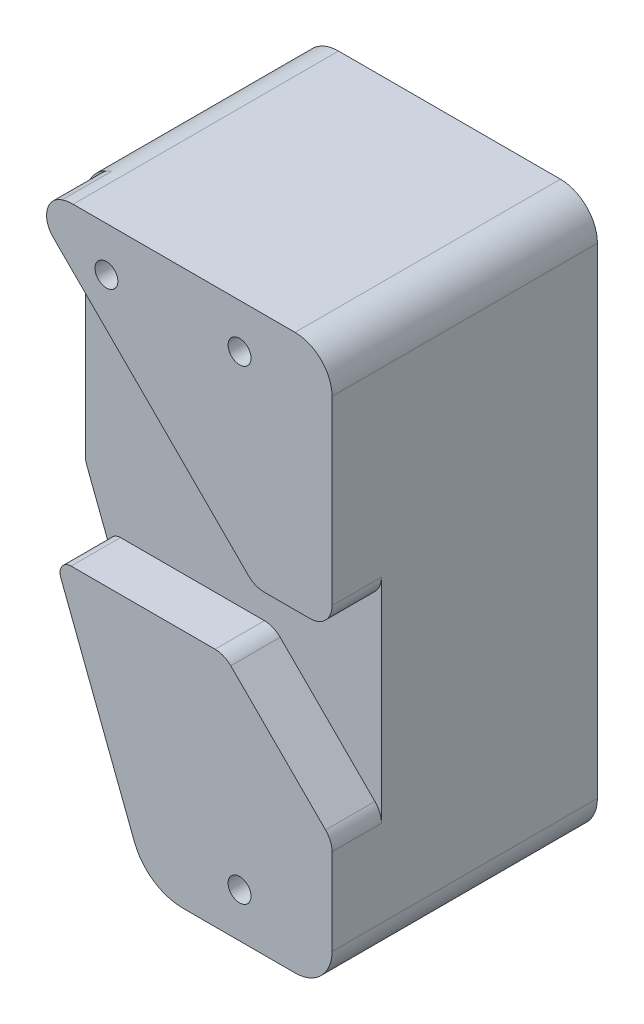
SolidWorks part; units mm, degrees
ref_plane "Front Plane" through (0, 0, 0) normal (0, 0, 1) x (1, 0, 0)
ref_plane "Top Plane" through (0, 0, 0) normal (0, 1, 0) x (1, 0, 0)
ref_plane "Right Plane" through (0, 0, 0) normal (1, 0, 0) x (0, 0, -1)
sketch "Sketch1" plane through (0, 0, 0) normal (0, 0, 1) x (1, 0, 0)
  line L0 (12.5, 69) -> (12.5, 6) construction
  line L1 (0, 0) -> (25, 0)
  line L2 (0, 0) -> (0, 75)
  line L3 (0, 75) -> (25, 75)
  line L4 (25, 0) -> (25, 75)
  line L6 (0, 75) -> (-15, 75)
  line L7 (0, 75) -> (0, 37.5)
  line L8 (0, 37.5) -> (-15, 37.5)
  line L9 (-15, 75) -> (-15, 37.5)
  circle A0 centre (12.5, 69) radius 1.5
  circle A1 centre (12.5, 6) radius 1.5
  circle A2 centre (12.5, 37.5) radius 1.5
  dimension "D3" = 3
  dimension "D4" = 3
  dimension "D7" = 3
  dimension "D1" = 75
  dimension "D2" = 25
  dimension "D5" = 6
  dimension "D6" = 6
  dimension "D8" = 0
  dimension "D9" = 12.5
  dimension "D10" = 15
extrude "Boss-Extrude1" add sketch "Sketch1" along normal blind 2.85 contours L6 L9 L8 L2 | L1 L4 L3 L2 A0 A2 A1 region at (0.7906, 18.75, 0) region at (-7.5, 56.25, 0)
fillet "Fillet1" radius 5 5 edges at (25, 0, 1.425) (0, 0, 1.425) (25, 75, 1.425) (-15, 75, 1.425) (0, 37.5, 1.425)
fillet "Fillet2" radius 2 1 edges at (-15, 37.5, 1.425)
sketch "Sketch5" plane through (0, 0, 2.85) normal (0, 0, 1) x (1, 0, 0)
  line L0 (0, 25) -> (25, 50)
  line L3 (-17.5, 42.5) -> (42.5, 42.5)
  line L4 (42.5, 32.5) -> (42.5, 42.5)
  line L5 (-0.8417, 35.2764) -> (42.5, 42.5) construction
  line L6 (-17.5, 42.5) -> (42.5, 32.5) construction
  line L7 (0, 17.9289) -> (25, 42.9289)
  line L8 (0, 32.0711) -> (21.4645, 53.5355)
  line L9 (-20.8226, 11.2484) -> (21.4645, 53.5355) construction
  line L10 (-17.2871, 7.7129) -> (25, 50) construction
  line L11 (-13.7516, 4.1774) -> (28.5355, 46.4645) construction
  line L12 (21.4645, 53.5355) -> (25, 57.0711)
  line L13 (-15, 70) -> (-15, 39.5)
  line L14 (-13, 37.5) -> (-5, 37.5)
  line L15 (0, 32.5) -> (0, 5)
  line L16 (5, 0) -> (20, 0)
  line L17 (25, 5) -> (25, 70)
  line L18 (20, 75) -> (-10, 75)
  line L19 (-15, 70) -> (-15, 39.5)
  line L20 (-13, 37.5) -> (-5, 37.5)
  line L21 (0, 32.5) -> (0, 5)
  line L22 (5, 0) -> (20, 0)
  line L23 (25, 5) -> (25, 70)
  line L24 (20, 75) -> (-10, 75)
  line L25 (42.5, 32.5) -> (14.5711, 32.5)
  arc A6 (-15, 39.5) -> (-13, 37.5) centre (-13, 39.5) ccw
  arc A7 (0, 32.5) -> (-5, 37.5) centre (-5, 32.5) ccw
  arc A8 (0, 5) -> (5, 0) centre (5, 5) ccw
  arc A9 (20, 0) -> (25, 5) centre (20, 5) ccw
  arc A10 (25, 70) -> (20, 75) centre (20, 70) ccw
  arc A11 (-10, 75) -> (-15, 70) centre (-10, 70) ccw
  arc A12 (-15, 39.5) -> (-13, 37.5) centre (-13, 39.5) ccw
  arc A13 (0, 32.5) -> (-5, 37.5) centre (-5, 32.5) ccw
  arc A14 (0, 5) -> (5, 0) centre (5, 5) ccw
  arc A15 (20, 0) -> (25, 5) centre (20, 5) ccw
  arc A16 (25, 70) -> (20, 75) centre (20, 70) ccw
  arc A17 (-10, 75) -> (-15, 70) centre (-10, 70) ccw
  point P0 (12.5, 37.5)
  point P9 (12.5, 37.5)
  line M2 (-15, 70) -> (-15, 39.5)
  line M6 (0, 32.5) -> (0, 5)
  arc M7 (0, 5) -> (5, 0) centre (5, 5) ccw
  line M8 (5, 0) -> (20, 0)
  arc M9 (20, 0) -> (25, 5) centre (20, 5) ccw
  line M10 (25, 5) -> (25, 70)
  arc M11 (25, 70) -> (20, 75) centre (20, 70) ccw
  line M12 (20, 75) -> (-10, 75)
  arc M13 (-10, 75) -> (-15, 70) centre (-10, 70) ccw
  circle M15 centre (12.5, 6) radius 1.5
  circle M16 centre (12.5, 69) radius 1.5
  dimension "D3" = 0
  dimension "D4" = 5
  dimension "D5" = 5
extrude "Boss-Extrude2" add sketch "Sketch5" along normal blind 3.5 contours L8 L12 L3 M10 M11 M12 M13 M2 M16 | L25 L7 M10 M6 M7 M8 M9 M15 region at (13.6784, 14.8345, 2.85) region at (3.588, 59.5787, 2.85)
fillet "Fillet3" radius 3.5 2 edges at (14.5711, 32.5, 4.6) (10.4289, 42.5, 4.6)
fillet "Fillet4" radius 2 1 edges at (-15, 42.5, 4.6)
fillet "Fillet5" radius 2 3 edges at (0, 17.9289, 4.6) (25, 32.5, 4.6) (25, 57.0711, 4.6)
sketch "Sketch6" plane through (0, 0, 6.35) normal (0, 0, 1) x (1, 0, 0)
  circle A0 centre (-5.5, 69) radius 1.5
  circle A1 centre (12.5, 69) radius 1.5 construction
  dimension "D1" = 3
  dimension "D2" = 18
extrude "Cut-Extrude1" cut sketch "Sketch6" against normal blind 10
sketch "Sketch8" plane through (0, 0, 0) normal (0, 0, -1) x (-1, 0, 0)
  line L6 (5, 37.5) -> (13, 37.5)
  line L7 (15, 39.5) -> (15, 70)
  line L8 (10, 75) -> (-20, 75)
  line L9 (-25, 70) -> (-25, 5)
  line L10 (-20, 0) -> (-5, 0)
  line L11 (0, 5) -> (0, 32.5)
  line L12 (5, 37.5) -> (13, 37.5)
  line L13 (15, 39.5) -> (15, 70)
  line L14 (10, 75) -> (-20, 75)
  line L15 (-25, 70) -> (-25, 5)
  line L16 (-20, 0) -> (-5, 0)
  line L17 (0, 5) -> (0, 32.5)
  arc A6 (13, 37.5) -> (15, 39.5) centre (13, 39.5) ccw
  arc A7 (15, 70) -> (10, 75) centre (10, 70) ccw
  arc A8 (-20, 75) -> (-25, 70) centre (-20, 70) ccw
  arc A9 (-25, 5) -> (-20, 0) centre (-20, 5) ccw
  arc A10 (-5, 0) -> (0, 5) centre (-5, 5) ccw
  arc A11 (5, 37.5) -> (0, 32.5) centre (5, 32.5) ccw
  arc A12 (13, 37.5) -> (15, 39.5) centre (13, 39.5) ccw
  arc A13 (15, 70) -> (10, 75) centre (10, 70) ccw
  arc A14 (-20, 75) -> (-25, 70) centre (-20, 70) ccw
  arc A15 (-25, 5) -> (-20, 0) centre (-20, 5) ccw
  arc A16 (-5, 0) -> (0, 5) centre (-5, 5) ccw
  arc A17 (5, 37.5) -> (0, 32.5) centre (5, 32.5) ccw
  circle M13 centre (5.5, 69) radius 1.5
  line M14 (5, 37.5) -> (13, 37.5)
  arc M15 (13, 37.5) -> (15, 39.5) centre (13, 39.5) ccw
  line M16 (15, 39.5) -> (15, 70)
  arc M17 (15, 70) -> (10, 75) centre (10, 70) ccw
  line M18 (10, 75) -> (-20, 75)
  arc M19 (-20, 75) -> (-25, 70) centre (-20, 70) ccw
  line M20 (-25, 70) -> (-25, 5)
  arc M21 (-25, 5) -> (-20, 0) centre (-20, 5) ccw
  line M22 (-20, 0) -> (-5, 0)
  arc M23 (-5, 0) -> (0, 5) centre (-5, 5) ccw
  line M24 (0, 5) -> (0, 32.5)
  arc M25 (0, 32.5) -> (5, 37.5) centre (5, 32.5) cw
  circle M26 centre (-12.5, 37.5) radius 1.5
  circle M27 centre (-12.5, 6) radius 1.5
  circle M28 centre (-12.5, 69) radius 1.5
  dimension "D1" = 0
extrude "Boss-Extrude3" add sketch "Sketch8" along normal blind 6.35 contours M25 M14 M15 M16 M17 M18 M19 M20 M21 M22 M23 M24 M27 M28 M26 M13 region at (7.8634, 41.813, 0)
sketch "Sketch9" plane through (0, 0, 6.35) normal (0, 0, 1) x (1, 0, 0)
  line L0 (13.5459, 31.4749) -> (0.5858, 18.5147) construction
  line L1 (0, 17.1005) -> (0, 5) construction
  line L2 (5, 0) -> (20, 0) construction
  line L3 (25, 5) -> (25, 30.5) construction
  line L4 (23, 32.5) -> (16.0208, 32.5) construction
  line L5 (11.4541, 43.5251) -> (24.4142, 56.4853) construction
  line L6 (25, 57.8995) -> (25, 70) construction
  line L7 (20, 75) -> (-10, 75) construction
  line L8 (-15, 70) -> (-15, 44.5) construction
  line L9 (-13, 42.5) -> (8.9792, 42.5) construction
  line L10 (13.5459, 31.4749) -> (0.5858, 18.5147)
  line L11 (0, 17.1005) -> (0, 5)
  line L12 (5, 0) -> (20, 0)
  line L13 (25, 5) -> (25, 30.5)
  line L14 (23, 32.5) -> (16.0208, 32.5)
  line L15 (11.4541, 43.5251) -> (24.4142, 56.4853)
  line L16 (25, 57.8995) -> (25, 70)
  line L17 (20, 75) -> (-10, 75)
  line L18 (-15, 70) -> (-15, 44.5)
  line L19 (-13, 42.5) -> (8.9792, 42.5)
  arc A0 (0.5858, 18.5147) -> (0, 17.1005) centre (2, 17.1005) ccw construction
  arc A1 (0, 5) -> (5, 0) centre (5, 5) ccw construction
  arc A2 (20, 0) -> (25, 5) centre (20, 5) ccw construction
  arc A3 (25, 30.5) -> (23, 32.5) centre (23, 30.5) ccw construction
  arc A4 (16.0208, 32.5) -> (13.5459, 31.4749) centre (16.0208, 29) ccw construction
  arc A5 (24.4142, 56.4853) -> (25, 57.8995) centre (23, 57.8995) ccw construction
  arc A6 (25, 70) -> (20, 75) centre (20, 70) ccw construction
  arc A7 (-10, 75) -> (-15, 70) centre (-10, 70) ccw construction
  arc A8 (-15, 44.5) -> (-13, 42.5) centre (-13, 44.5) ccw construction
  arc A9 (8.9792, 42.5) -> (11.4541, 43.5251) centre (8.9792, 46) ccw construction
  arc A10 (0.5858, 18.5147) -> (0, 17.1005) centre (2, 17.1005) ccw
  arc A11 (0, 5) -> (5, 0) centre (5, 5) ccw
  arc A12 (20, 0) -> (25, 5) centre (20, 5) ccw
  arc A13 (25, 30.5) -> (23, 32.5) centre (23, 30.5) ccw
  arc A14 (16.0208, 32.5) -> (13.5459, 31.4749) centre (16.0208, 29) ccw
  arc A15 (24.4142, 56.4853) -> (25, 57.8995) centre (23, 57.8995) ccw
  arc A16 (25, 70) -> (20, 75) centre (20, 70) ccw
  arc A17 (-10, 75) -> (-15, 70) centre (-10, 70) ccw
  arc A18 (-15, 44.5) -> (-13, 42.5) centre (-13, 44.5) ccw
  arc A19 (8.9792, 42.5) -> (11.4541, 43.5251) centre (8.9792, 46) ccw
  circle M1 centre (-5.5, 69) radius 1.5
  circle M2 centre (12.5, 69) radius 1.5
  line M3 (11.4541, 43.5251) -> (24.4142, 56.4853)
  arc M4 (24.4142, 56.4853) -> (25, 57.8995) centre (23, 57.8995) ccw
  line M5 (25, 57.8995) -> (25, 70)
  arc M6 (25, 70) -> (20, 75) centre (20, 70) ccw
  line M7 (20, 75) -> (-10, 75)
  arc M8 (-10, 75) -> (-15, 70) centre (-10, 70) ccw
  line M9 (-15, 70) -> (-15, 44.5)
  arc M10 (-15, 44.5) -> (-13, 42.5) centre (-13, 44.5) ccw
  line M11 (-13, 42.5) -> (8.9792, 42.5)
  arc M12 (8.9792, 42.5) -> (11.4541, 43.5251) centre (8.9792, 46) ccw
extrude "Boss-Extrude4" add sketch "Sketch9" along normal blind 3.175 contours M12 M3 M4 M5 M6 M7 M8 M9 M10 M11 M2 M1 | L14 A14 L10 A10 L11 A11 L12 A12 L13 A13 region at (13.6542, 14.7163, 6.35) region at (3.6533, 59.5379, 6.35)
sketch "Sketch10" plane through (0, 0, 9.525) normal (0, 0, 1) x (1, 0, 0)
  line L1 (25, 57.8995) -> (-15, 57.8995)
  line L2 (25, 57.8995) -> (25, 42.5)
  line L3 (25, 42.5) -> (-15, 42.5)
  line L4 (-15, 57.8995) -> (-15, 42.5)
  line L5 (25, 32.5) -> (0, 32.5)
  line L6 (25, 32.5) -> (25, 17.1005)
  line L7 (25, 17.1005) -> (0, 17.1005)
  line L8 (0, 32.5) -> (0, 17.1005)
  point P0 (-13, 42.5)
  point P1 (-15, 44.5)
  point P8 (25, 32.5)
extrude "Boss-Extrude5" add sketch "Sketch10" against normal up to surface (6.675 mm away) up to face at (5.4763, 37.3513, 2.85)
sketch "Sketch11" plane through (0, 0, 9.525) normal (0, 0, 1) x (1, 0, 0)
  line L0 (8.9645, 33.9645) -> (0.4289, 42.5)
  line L1 (-15, 42.5) -> (25, 42.5) construction
  line L2 (16.0355, 41.0355) -> (25, 32.0711)
  line L3 (16.0355, 41.0355) -> (-14.6824, 71.7535)
  line L4 (8.9645, 33.9645) -> (25, 17.9289)
  line L5 (0.4289, 42.5) -> (-15, 42.5)
  line L6 (-15, 70) -> (-15, 42.5) construction
  line L7 (-15, 70) -> (-15, 42.5)
  line L8 (25, 5) -> (25, 32.5) construction
  line L9 (25, 17.9289) -> (25, 32.5)
  line L10 (24.2965, 32.7746) -> (25.447, 33.2672)
  line L11 (25.447, 33.2672) -> (25, 32.0711)
  arc A0 (-10, 75) -> (-15, 70) centre (-10, 70) ccw construction
  arc A1 (-14.6824, 71.7535) -> (-15, 70) centre (-10, 70) ccw
  line M2 (-15, 70) -> (-15, 42.5)
  line M3 (-15, 42.5) -> (25, 42.5)
  arc M7 (-10, 75) -> (-15, 70) centre (-10, 70) ccw
extrude "Cut-Extrude2" cut sketch "Sketch11" against normal up to surface (6.675 mm away) contours L3 M3 M7 M2 | L4 L9 L2 L3 L0 M3 | L11 L10 L2 region at (15.7738, 33.2738, 9.525) region at (-5.1378, 52.3468, 9.525) region at (24.9145, 32.7043, 9.525) up to face at (0.3745, 37.8745, 2.85)
sketch "Sketch12" plane through (0, 0, -6.35) normal (0, 0, -1) x (-1, 0, 0)
  line L0 (0, 0) -> (14.8675, 38.7841)
  line L1 (-5, 0) -> (0, 0)
  line L2 (5, 37.5) -> (13, 37.5) construction
  line L3 (0, 5) -> (0, 32.5) construction
  line L4 (5, 37.5) -> (13, 37.5)
  line L5 (0, 5) -> (0, 32.5)
  arc A0 (13, 37.5) -> (15, 39.5) centre (13, 39.5) ccw construction
  arc A1 (13, 37.5) -> (14.8675, 38.7841) centre (13, 39.5) ccw
  arc A2 (-5, 0) -> (0, 5) centre (-5, 5) ccw construction
  arc A3 (5, 37.5) -> (0, 32.5) centre (5, 32.5) ccw construction
  arc A4 (5, 37.5) -> (0, 32.5) centre (5, 32.5) ccw
  arc A5 (-5, 0) -> (0, 5) centre (-5, 5) ccw
extrude "Boss-Extrude6" add sketch "Sketch12" against normal up to surface (9.2 mm away) up to face at (1.286, 42.4818, 2.85)
fillet "Fillet6" radius 7 1 edges at (0, 0, -1.75)
sketch "Sketch13" plane through (0, 0, 9.525) normal (0, 0, 1) x (1, 0, 0)
  line L0 (0, 32.5) -> (0, 5) construction
  line L1 (-1.7229, 4.4944) -> (-14.8675, 38.7841) construction
  line L2 (0, 32.5) -> (0, 5)
  line L3 (-1.7229, 4.4944) -> (-12.4585, 32.5)
  line L4 (0, 32.5) -> (-12.4585, 32.5)
  line L5 (4.8133, 0) -> (5, 0)
  arc A0 (0, 5) -> (5, 0) centre (5, 5) ccw construction
  arc A1 (-1.7229, 4.4944) -> (4.8133, 0) centre (4.8133, 7) ccw construction
  arc A2 (0, 5) -> (5, 0) centre (5, 5) ccw
  arc A3 (-1.7229, 4.4944) -> (4.8133, 0) centre (4.8133, 7) ccw
extrude "Boss-Extrude7" add sketch "Sketch13" against normal up to surface (6.675 mm away) up to face at (1.6689, 30.4168, 2.85)
fillet "Fillet7" radius 3 5 edges at (25, 42.5, 6.1875) (25, 17.9289, 6.1875) (10.4289, 32.5, 6.1875) (14.5711, 42.5, 6.1875) (-14.6824, 71.7535, 6.1875)
fillet "Fillet8" radius 1.5 1 edges at (-12.4585, 32.5, 6.1875)
sketch "Sketch14" plane through (0, 0, -6.35) normal (0, 0, -1) x (-1, 0, 0)
  circle A0 centre (-12.5, 6) radius 1.5
extrude "Cut-Extrude3" cut sketch "Sketch14" against normal through all
sketch "Sketch15" plane through (0, 0, -6.35) normal (0, 0, -1) x (-1, 0, 0)
  circle A0 centre (-12.5, 69) radius 1.55
  circle A1 centre (5.5, 69) radius 1.55
  circle A2 centre (-12.5, 37.5) radius 1.55
  circle A3 centre (-12.5, 6) radius 1.55
  dimension "D1" = 3.1
  dimension "D2" = 3.1
  dimension "D3" = 3.1
  dimension "D4" = 3.1
extrude "Cut-Extrude4" cut sketch "Sketch15" against normal through all
sketch "Sketch16" plane through (0, 0, -6.35) normal (0, 0, -1) x (-1, 0, 0)
  line L5 (-20, 0) -> (-4.8133, 0)
  line L6 (1.7229, 4.4944) -> (14.8675, 38.7841)
  line L7 (15, 39.5) -> (15, 70)
  line L8 (10, 75) -> (-20, 75)
  line L9 (-25, 70) -> (-25, 5)
  line L10 (-20, 0) -> (-4.8133, 0)
  line L11 (1.7229, 4.4944) -> (14.8675, 38.7841)
  line L12 (15, 39.5) -> (15, 70)
  line L13 (10, 75) -> (-20, 75)
  line L14 (-25, 70) -> (-25, 5)
  circle A0 centre (-12.5, 6) radius 1.55 construction
  circle A1 centre (-12.5, 37.5) radius 1.55 construction
  circle A2 centre (5.5, 69) radius 1.55 construction
  circle A3 centre (-12.5, 69) radius 1.55 construction
  circle A4 centre (-12.5, 6) radius 1.55
  arc A5 (-4.8133, 0) -> (1.7229, 4.4944) centre (-4.8133, 7) ccw
  arc A6 (14.8675, 38.7841) -> (15, 39.5) centre (13, 39.5) ccw
  arc A7 (15, 70) -> (10, 75) centre (10, 70) ccw
  arc A8 (-20, 75) -> (-25, 70) centre (-20, 70) ccw
  arc A9 (-25, 5) -> (-20, 0) centre (-20, 5) ccw
  arc A10 (-4.8133, 0) -> (1.7229, 4.4944) centre (-4.8133, 7) ccw
  arc A11 (14.8675, 38.7841) -> (15, 39.5) centre (13, 39.5) ccw
  arc A12 (15, 70) -> (10, 75) centre (10, 70) ccw
  arc A13 (-20, 75) -> (-25, 70) centre (-20, 70) ccw
  arc A14 (-25, 5) -> (-20, 0) centre (-20, 5) ccw
  circle A15 centre (-12.5, 37.5) radius 1.55
  circle A16 centre (5.5, 69) radius 1.55
  circle A17 centre (-12.5, 69) radius 1.55
  dimension "D1" = 0
extrude "Boss-Extrude8" add sketch "Sketch16" along normal blind 20
